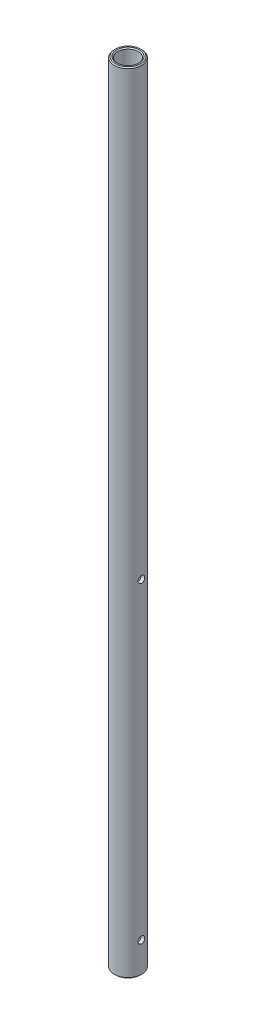
SolidWorks part; units mm, degrees
material "AISI 304"
ref_plane "Спереди" through (0, 0, 0) normal (0, 0, 1) x (1, 0, 0)
ref_plane "Сверху" through (0, 0, 0) normal (0, 1, 0) x (1, 0, 0)
ref_plane "Справа" through (0, 0, 0) normal (1, 0, 0) x (0, 0, -1)
other "Configuration Table"
sketch "Эскиз1" plane through (0, 0, 0) normal (0, 1, 0) x (1, 0, 0)
  circle A0 centre (0, 0) radius 4
  circle A1 centre (0, 0) radius 3
  dimension "D1" = 8
  dimension "D2" = 6
extrude "Бобышка-Вытянуть1" add sketch "Эскиз1" along normal blind 230
chamfer "Фаска1" distance 0.3 angle 45 4 edges at (0, 230, 3) (0, 0, 3) (0, 0, 4) (0, 230, 4)
sketch "Эскиз2" plane through (0, 0, 0) normal (1, 0, 0) x (0, 0, -1)
  circle A0 centre (0, 9) radius 1 construction
  circle A1 centre (0, 9) radius 1
extrude "Вырез-Вытянуть1" cut sketch "Эскиз2" against normal through all both and the other way through all
sketch "Эскиз3" plane through (0, 0, 0) normal (1, 0, 0) x (0, 0, -1)
  circle A0 centre (0, 100) radius 1.25 construction
  circle A3 centre (0, 9) radius 1 construction
  circle A4 centre (0, 9) radius 1 construction
  circle A5 centre (0, 100) radius 1.25 construction
  circle A6 centre (0, 100) radius 1
  dimension "D1" = 2
extrude "Вырез-Вытянуть2" cut sketch "Эскиз3" against normal through all both and the other way through all
